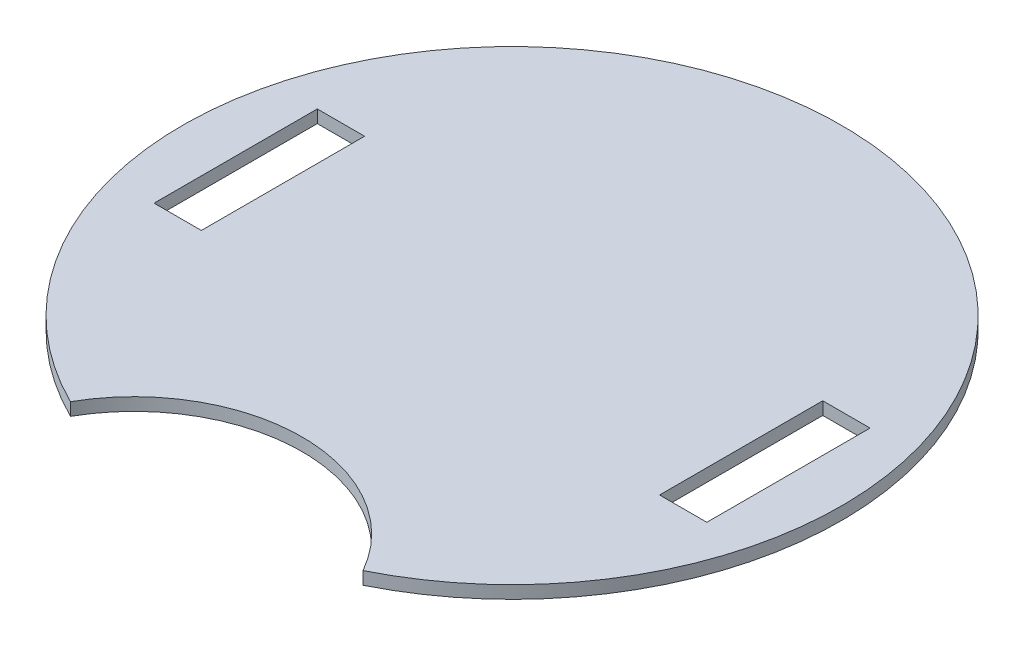
SolidWorks part; units mm, degrees
ref_plane "Front Plane" through (0, 0, 0) normal (0, 0, 1) x (1, 0, 0)
ref_plane "Top Plane" through (0, 0, 0) normal (0, 1, 0) x (1, 0, 0)
ref_plane "Right Plane" through (0, 0, 0) normal (1, 0, 0) x (0, 0, -1)
sketch "Sketch1" plane through (0, 0, 0) normal (0, 1, 0) x (1, 0, 0)
  line L0 (0, -86.0416) -> (-33.2911, -67.2064) construction
  line L1 (0, -86.0416) -> (0, 0) construction
  arc A0 (33.2911, -67.2064) -> (-33.2911, -67.2064) centre (0, 0) ccw
  arc A1 (33.2911, -67.2064) -> (-33.2911, -67.2064) centre (0, -86.0416) ccw
  dimension "D1" = 150
  dimension "D2" = 76.5
  dimension "D3" = 60.5
extrude "Boss-Extrude1" add sketch "Sketch1" along normal blind 2.9
sketch "solenoid placement" plane through (0, 2.9, 0) normal (0, 1, 0) x (1, 0, 0)
  line L0 (0, 0) -> (0, -36) construction
  line L1 (0, -36) -> (0, -47.7916) construction
  line L2 (-19, -36) -> (19, -36)
  line L3 (-19, -36) -> (-19, 28.4)
  line L4 (-19, 28.4) -> (19, 28.4)
  line L5 (19, -36) -> (19, 28.4)
  circle A1 centre (0, 0) radius 75 construction
  arc A2 (33.2911, -67.2064) -> (-33.2911, -67.2064) centre (0, 0) ccw construction
  arc A3 (33.2911, -67.2064) -> (-33.2911, -67.2064) centre (0, -86.0416) ccw construction
  dimension "D1" = 64.4
  dimension "D2" = 36
  dimension "D4" = 38
sketch "Sketch2" plane through (0, 2.9, 0) normal (0, 1, 0) x (1, 0, 0)
  line L1 (-62.5975, 18.2695) -> (-52.4375, 18.2695) construction
  line L2 (-62.5975, 18.2695) -> (-62.5975, -18.2695) construction
  line L3 (-62.5975, -18.2695) -> (-52.4375, -18.2695) construction
  line L4 (-52.4375, 18.2695) -> (-52.4375, -18.2695) construction
  line L8 (-62.8975, -18.5695) -> (-52.1375, -18.5695)
  line L9 (-52.1375, 18.5695) -> (-52.1375, -18.5695)
  line L10 (-62.8975, 18.5695) -> (-52.1375, 18.5695)
  line L11 (-62.8975, 18.5695) -> (-62.8975, -18.5695)
  line L12 (0, 0) -> (0, 75) construction
  line L13 (52.4375, 18.2695) -> (52.4375, -18.2695) construction
  line L14 (62.5975, -18.2695) -> (52.4375, -18.2695) construction
  line L15 (62.5975, 18.2695) -> (62.5975, -18.2695) construction
  line L16 (62.5975, 18.2695) -> (52.4375, 18.2695) construction
  line L17 (62.8975, 18.5695) -> (62.8975, -18.5695)
  line L18 (62.8975, 18.5695) -> (52.1375, 18.5695)
  line L19 (52.1375, 18.5695) -> (52.1375, -18.5695)
  line L20 (62.8975, -18.5695) -> (52.1375, -18.5695)
  arc A0 (33.2911, -67.2064) -> (-33.2911, -67.2064) centre (0, 0) ccw construction
extrude "Cut-Extrude1" cut sketch "Sketch2" against normal through all
equation "\"smallPulleyTeeth\"= 15"
equation "\"largePulleyTeeth\"= 30"
equation "\"eighthThick\"= 2.9mm"
equation "\"sixteenthThick\" = 1.7mm"
equation "\"wheelEighthThick\"=3.0mm"
equation "\"quarterThick\"=5.6mm"
equation "\"OD\" = 150mm"
equation "\"puckAngle\" = 60.5deg"
equation "\"D1@Sketch1\"=\"OD\""
equation "\"puckDiam\" = 76.5mm"
equation "\"D2@Sketch1\"=\"puckDiam\""
equation "\"D3@Sketch1\"=\"puckAngle\""
equation "\"D1@Boss-Extrude1\"=\"eighthThick\""
equation "\"axlePress\" = 5.8mm"
equation "\"press\" = 0.3mm"
equation "\"wheelClear\" = 0.3mm"
equation "\"D1@Sketch2\"=\"wheelClear\""
